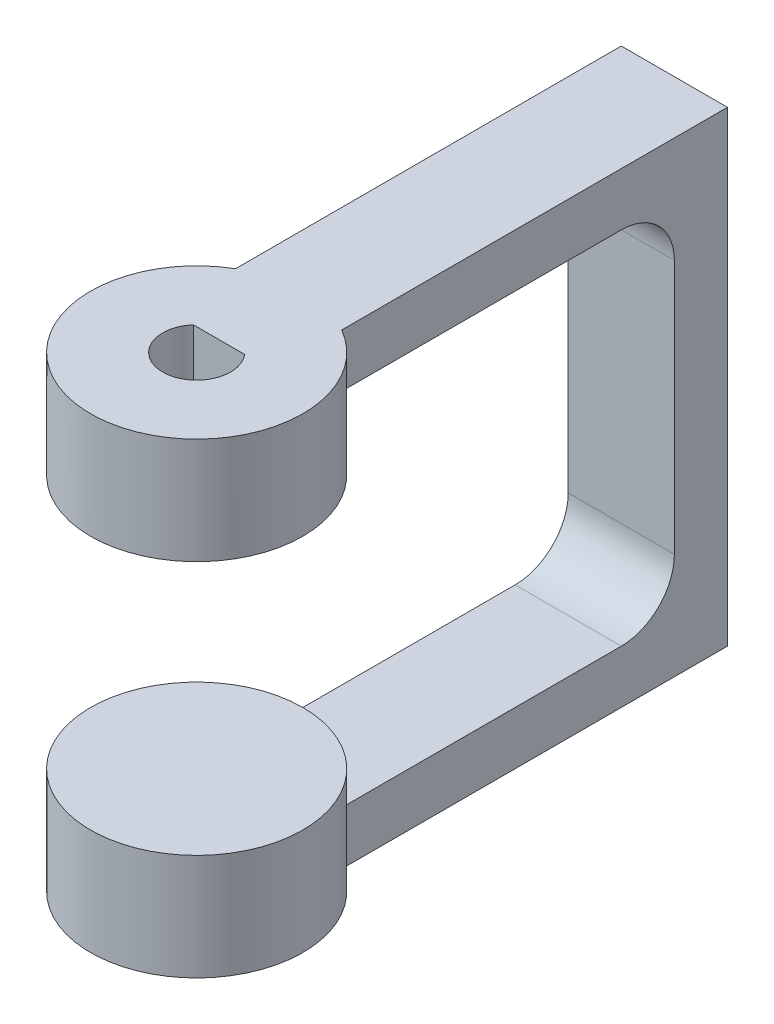
SolidWorks part; units mm, degrees
ref_plane "Front Plane" through (0, 0, 0) normal (0, 0, 1) x (1, 0, 0)
ref_plane "Top Plane" through (0, 0, 0) normal (0, 1, 0) x (1, 0, 0)
ref_plane "Right Plane" through (0, 0, 0) normal (1, 0, 0) x (0, 0, -1)
sketch "Sketch1" plane through (0, 0, 0) normal (0, 1, 0) x (1, 0, 0)
  circle A0 centre (0, 0) radius 12.7
  dimension "D1" = 25.4
extrude "Boss-Extrude1" add sketch "Sketch1" along normal mid plane 55.8292
sketch "Sketch4" plane through (0, 0, 0) normal (0, 0, 1) x (1, 0, 0)
  line L0 (-24.5861, 0) -> (49.9861, 0) construction
  line L1 (-12.7, 27.9146) -> (-12.7, -27.9146) construction
  line L2 (-12.7, 15.2146) -> (12.7, 15.2146)
  line L3 (-12.7, 15.2146) -> (-12.7, -15.2146)
  line L4 (-12.7, -15.2146) -> (12.7, -15.2146)
  line L5 (12.7, 15.2146) -> (12.7, -15.2146)
  point P7 (12.7, 0)
  point P8 (0, 15.2146)
  dimension "D1" = 30.4292
extrude "Cut-Extrude2" cut sketch "Sketch4" against normal through all both and the other way through all
sketch "Sketch5" plane through (0, 0, 0) normal (1, 0, 0) x (0, 0, -1)
  line L0 (-21.6052, 0) -> (34.6887, 0) construction
  line L1 (0, 27.9146) -> (57.15, 27.9146)
  line L2 (57.15, 27.9146) -> (57.15, -27.9146)
  line L4 (50.8, -21.5646) -> (50.8, 21.5646)
  line L5 (50.8, 21.5646) -> (0, 21.5646)
  line L6 (0, 21.5646) -> (0, 27.9146)
  line L7 (12.7, 27.9146) -> (-12.7, 27.9146) construction
  line L8 (0, -27.9146) -> (57.15, -27.9146)
  line L9 (50.8, -21.5646) -> (0, -21.5646)
  line L10 (0, -21.5646) -> (0, -27.9146)
  point P12 (50.8, 0)
  point P13 (57.15, 0)
  dimension "D1" = 6.35
  dimension "D2" = 6.35
  dimension "D3" = 57.15
extrude "Boss-Extrude2" add sketch "Sketch5" along normal mid plane 12.7
sketch "Sketch2" plane through (0, 27.9146, 0) normal (0, 1, 0) x (1, 0, 0)
  line L0 (-3.0665, 2.667) -> (3.0665, 2.667)
  arc A0 (-3.0665, 2.667) -> (3.0665, 2.667) centre (0, 0) ccw
  point P5 (0, -4.064)
  dimension "D1" = 8.128
  dimension "D2" = 6.731
extrude "Cut-Extrude3" cut sketch "Sketch2" against normal blind 10.16
mirror "Mirror1" about plane through (0, 0, 0) normal (0, 1, 0) of "Cut-Extrude3"
fillet "Fillet1" radius 6.35 2 edges at (0, -21.5646, -50.8) (0, 21.5646, -50.8)
